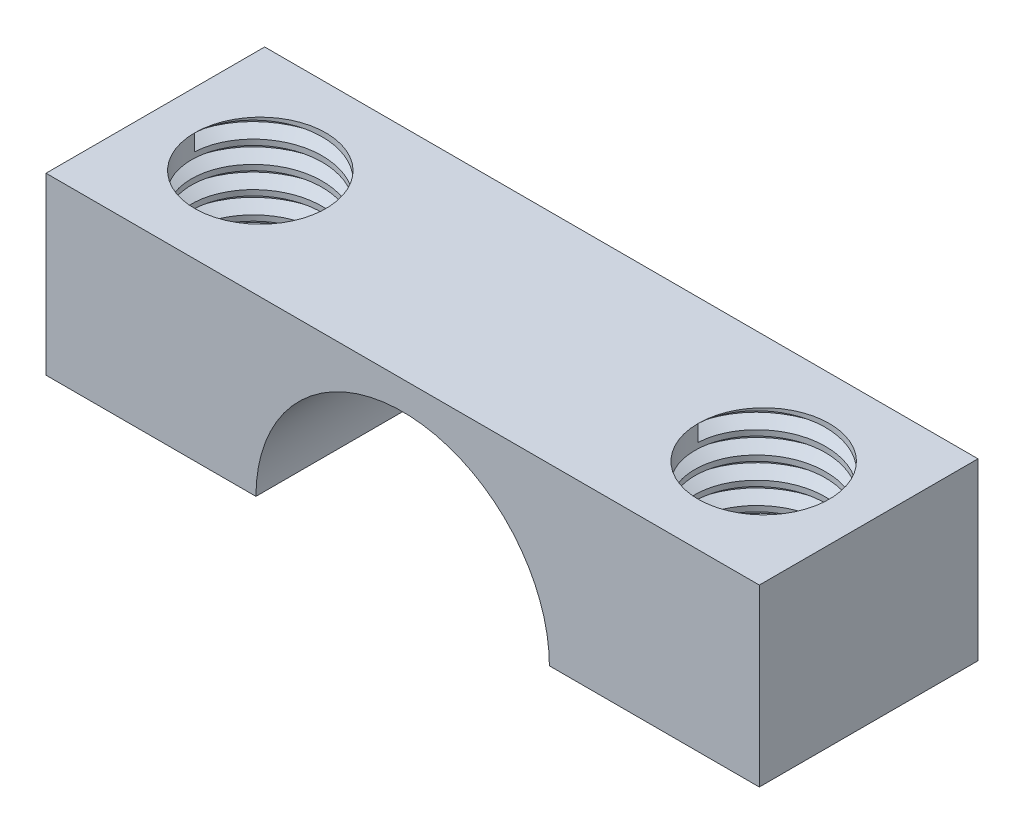
SolidWorks part; units mm, degrees
ref_plane "Front Plane" through (0, 0, 0) normal (0, 0, 1) x (1, 0, 0)
ref_plane "Top Plane" through (0, 0, 0) normal (0, 1, 0) x (1, 0, 0)
ref_plane "Right Plane" through (0, 0, 0) normal (1, 0, 0) x (0, 0, -1)
sketch "Sketch1" plane through (0, 0, 0) normal (0, 0, 1) x (1, 0, 0)
  line L1 (-8.155, -2) -> (8.155, -2)
  line L2 (-8.155, -2) -> (-8.155, 2)
  line L3 (-8.155, 2) -> (8.155, 2)
  line L4 (8.155, -2) -> (8.155, 2)
  line L5 (-8.155, -2) -> (8.155, 2) construction
  line L6 (-8.155, 2) -> (8.155, -2) construction
  point P0 (0, 0)
  dimension "D1" = 4
  dimension "D2" = 16.31
sketch "Sketch3" plane through (0, 0, 0) normal (0, 0, 1) x (1, 0, 0)
  line L0 (0, 0) -> (0, -2) construction
  line L1 (-8.155, -2) -> (8.155, -2) construction
  line L2 (-3.355, -2) -> (3.355, -2)
  line L3 (0, 1.355) -> (0, 2) construction
  line L4 (-8.155, 2) -> (8.155, 2) construction
  arc A0 (3.355, -2) -> (-3.355, -2) centre (0, -2) ccw
  point P8 (0, -2)
extrude "Boss-Extrude3" add sketch "Sketch1" against normal blind 5 contours L2 L3 L4 L1
extrude "Cut-Extrude9" cut sketch "Sketch3" against normal blind 5
sketch "Sketch4" plane through (0, 0, 0) normal (0, 1, 0) x (1, 0, 0)
  line L0 (0, 0) -> (0, 5) construction
  line L1 (-8.155, 0) -> (8.155, 0) construction
  line L2 (-8.155, 5) -> (8.155, 5) construction
  line L3 (0, 2.5) -> (5.755, 2.5) construction
  line L5 (0, 2.5) -> (-5.755, 2.5) construction
  circle A0 centre (-5.755, 2.5) radius 1.5
  circle A1 centre (5.755, 2.5) radius 1.5
extrude "Cut-Extrude10" cut sketch "Sketch4" against normal blind 2.5 and the other way blind 2.5 from offset 0
thread "Thread1" pitch 0.5 method cut profile "Thread Profile1" start angle 0, offset 0, length 5, pitch 0.5, diameter 3
ref_plane "Plane1" through (-7.255, 2, -2.5) normal (0, 0, 1) x (-1, 0, 0)
sketch "Thread Profile1" plane through (-7.255, 2, -2.5) normal (0, 0, 1) x (-1, 0, 0)
  line L0 (0, 0) -> (0, 0.5) construction
  line L1 (0, 0) -> (0.2706, 0.1562)
  line L2 (0.2706, 0.1562) -> (0.2706, 0.2187)
  line L3 (0.2706, 0.2187) -> (0, 0.375)
  line L4 (0.2706, 0.1875) -> (0, 0.1875) construction
  line L11 (0, 0) -> (0, 0.375)
  point P2 (0, 0)
  dimension "Pitch" = 0.5
  dimension "Profile_Angle" = 60
  dimension "Profile_Land" = 0.0625
  dimension "Profile_Height" = 0.2706
thread "Thread2" pitch 0.5 method cut profile "Thread Profile2" start angle 0, offset 0, length 5, pitch 0.5, diameter 3
ref_plane "Plane2" through (4.255, 2, -2.5) normal (0, 0, 1) x (-1, 0, 0)
sketch "Thread Profile2" plane through (4.255, 2, -2.5) normal (0, 0, 1) x (-1, 0, 0)
  line L0 (0, 0) -> (0, 0.5) construction
  line L1 (0, 0) -> (0.2706, 0.1562)
  line L2 (0.2706, 0.1562) -> (0.2706, 0.2187)
  line L3 (0.2706, 0.2187) -> (0, 0.375)
  line L4 (0.2706, 0.1875) -> (0, 0.1875) construction
  line L11 (0, 0) -> (0, 0.375)
  point P2 (0, 0)
  dimension "Pitch" = 0.5
  dimension "Profile_Angle" = 60
  dimension "Profile_Land" = 0.0625
  dimension "Profile_Height" = 0.2706
